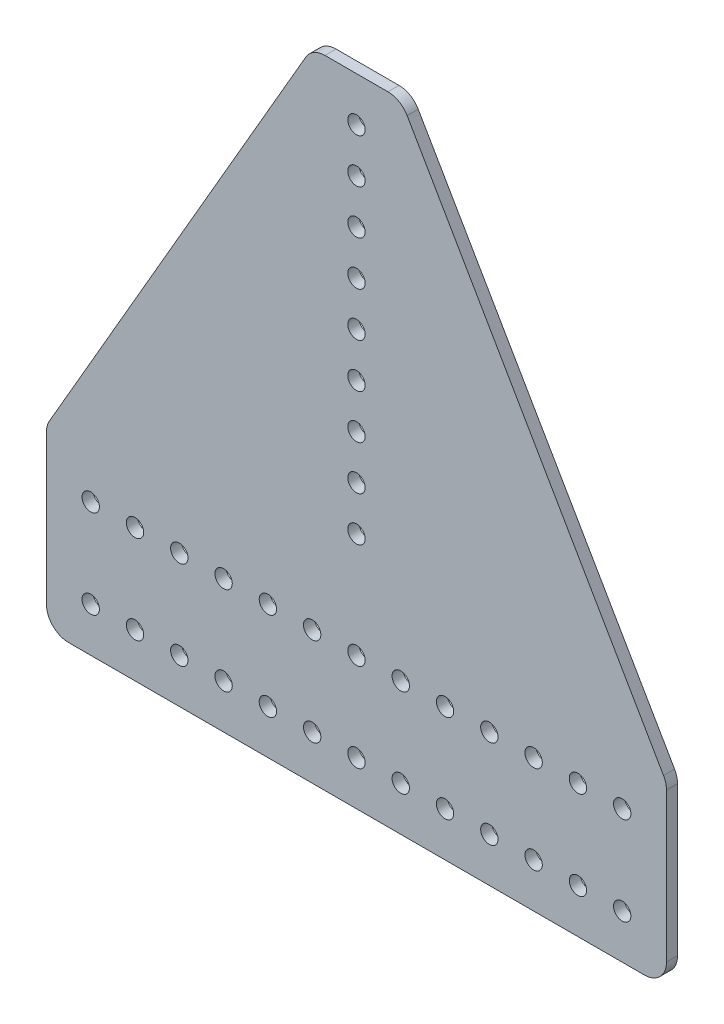
SolidWorks part; units mm, degrees
material "6061-T6 (SS)"
ref_plane "Front Plane" through (0, 0, 0) normal (0, 0, 1) x (1, 0, 0)
ref_plane "Top Plane" through (0, 0, 0) normal (0, 1, 0) x (1, 0, 0)
ref_plane "Right Plane" through (0, 0, 0) normal (1, 0, 0) x (0, 0, -1)
sketch "Sketch1" plane through (0, 0, 0) normal (0, 0, 1) x (1, 0, 0)
  line L0 (0, 0) -> (0, 50.8)
  line L1 (0, 50.8) -> (76.2, 182.5625)
  line L2 (76.2, 182.5625) -> (101.6, 182.5625)
  line L3 (101.6, 182.5625) -> (177.8, 50.8)
  line L4 (177.8, 50.8) -> (177.8, 0)
  line L5 (177.8, 0) -> (0, 0)
  point P3 (63.9651, 59.5342)
  point P8 (0, 0)
  point P9 (45.9287, 42.4394)
  point P10 (0, 0)
  point P11 (80.2411, 58.3166)
  point P12 (0, 0)
  point P13 (107.5851, 0)
  point P14 (0, 50.8)
  point P15 (50.8, 102.1508)
  dimension "D1" = 50.8
  dimension "D2" = 25.4
  dimension "D3" = 177.8
  dimension "D4" = 76.2
  dimension "D5" = 131.7625
extrude "Boss-Extrude1" add sketch "Sketch1" against normal blind 3.175 contours L1 L2 L3 L4 L5 L0
sketch "Sketch2" plane through (0, 0, 0) normal (0, 0, 1) x (1, 0, 0)
  line L0 (177.8, 0) -> (0, 0) construction
  line L1 (0, 0) -> (0, 50.8) construction
  line L2 (76.2, 182.5625) -> (101.6, 182.5625) construction
  circle A0 centre (12.7, 12.7) radius 2.4892
  circle A1 centre (25.4, 12.7) radius 2.4892
  circle A2 centre (38.1, 12.7) radius 2.4892
  circle A3 centre (50.8, 12.7) radius 2.4892
  circle A4 centre (63.5, 12.7) radius 2.4892
  circle A5 centre (76.2, 12.7) radius 2.4892
  circle A6 centre (88.9, 12.7) radius 2.4892
  circle A7 centre (101.6, 12.7) radius 2.4892
  circle A8 centre (114.3, 12.7) radius 2.4892
  circle A9 centre (127, 12.7) radius 2.4892
  circle A10 centre (139.7, 12.7) radius 2.4892
  circle A11 centre (152.4, 12.7) radius 2.4892
  circle A12 centre (165.1, 12.7) radius 2.4892
  circle A21 centre (25.4, 38.1) radius 2.4892
  circle A22 centre (38.1, 38.1) radius 2.4892
  circle A23 centre (50.8, 38.1) radius 2.4892
  circle A24 centre (63.5, 38.1) radius 2.4892
  circle A25 centre (76.2, 38.1) radius 2.4892
  circle A26 centre (88.9, 38.1) radius 2.4892
  circle A27 centre (101.6, 38.1) radius 2.4892
  circle A28 centre (114.3, 38.1) radius 2.4892
  circle A29 centre (127, 38.1) radius 2.4892
  circle A30 centre (139.7, 38.1) radius 2.4892
  circle A31 centre (152.4, 38.1) radius 2.4892
  circle A32 centre (165.1, 38.1) radius 2.4892
  circle A41 centre (12.7, 38.1) radius 2.4892
  circle A42 centre (88.9, 169.8625) radius 2.4892
  circle A43 centre (88.9, 157.1625) radius 2.4892
  circle A44 centre (88.9, 144.4625) radius 2.4892
  circle A45 centre (88.9, 131.7625) radius 2.4892
  circle A46 centre (88.9, 119.0625) radius 2.4892
  circle A47 centre (88.9, 106.3625) radius 2.4892
  circle A48 centre (88.9, 93.6625) radius 2.4892
  circle A49 centre (88.9, 80.9625) radius 2.4892
  circle A50 centre (88.9, 68.2625) radius 2.4892
  dimension "D1" = 4.9784
  dimension "D6" = 4.9784
  dimension "D2" = 12.7
  dimension "D3" = 12.7
  dimension "D7" = 12.7
  dimension "D8" = 12.7
  dimension "D4" = 13
  dimension "D5" = 2
  dimension "D9" = 9
extrude "Cut-Extrude1" cut sketch "Sketch2" against normal through all
fillet "Fillet1" radius 6.35 6 edges at (0, 0, -1.5875) (177.8, 0, -1.5875) (177.8, 50.8, -1.5875) (101.6, 182.5625, -1.5875) (0, 50.8, -1.5875) (76.2, 182.5625, -1.5875)
